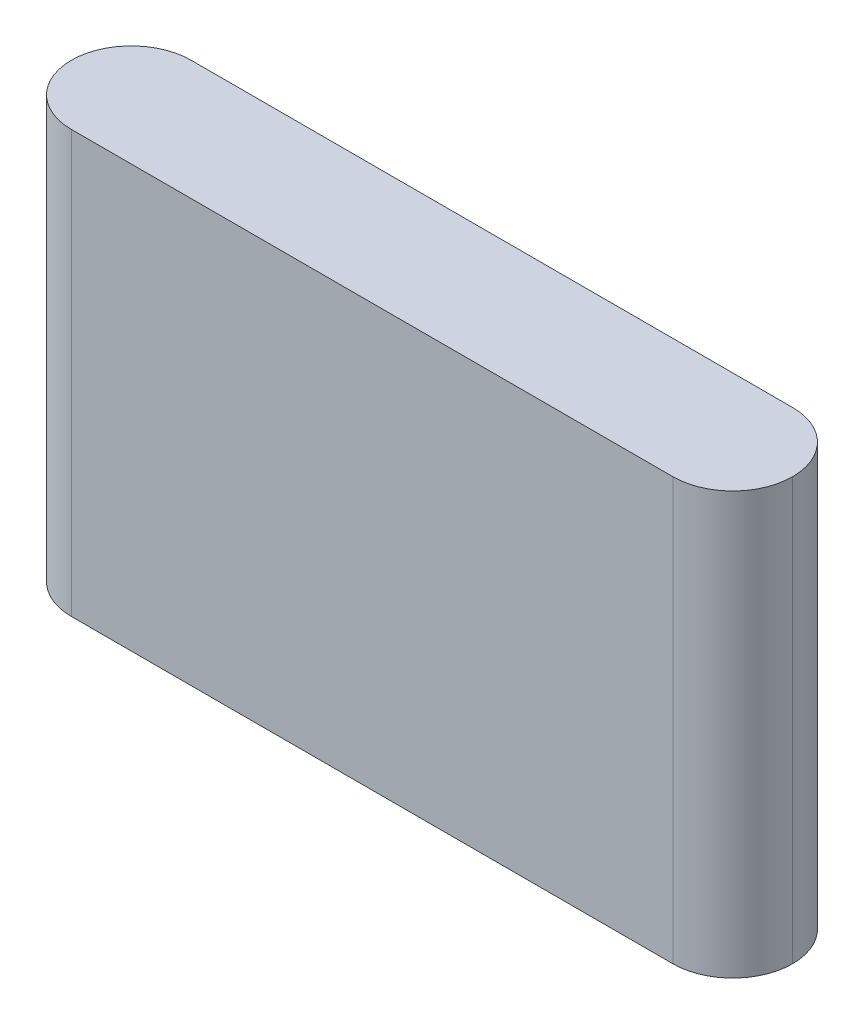
SolidWorks part; units mm, degrees
material "Custom Plastic"
ref_plane "Front Plane" through (0, 0, 0) normal (0, 0, 1) x (1, 0, 0)
ref_plane "Top Plane" through (0, 0, 0) normal (0, 1, 0) x (1, 0, 0)
ref_plane "Right Plane" through (0, 0, 0) normal (1, 0, 0) x (0, 0, -1)
sketch "Sketch1" plane through (0, 0, 0) normal (0, 1, 0) x (1, 0, 0)
  line L1 (-42.75, 7.1) -> (42.75, 7.1)
  line L2 (-42.75, 7.1) -> (-42.75, -7.1)
  line L3 (-42.75, -7.1) -> (42.75, -7.1)
  line L4 (42.75, 7.1) -> (42.75, -7.1)
  line L5 (-42.75, 7.1) -> (42.75, -7.1) construction
  line L6 (-42.75, -7.1) -> (42.75, 7.1) construction
  point P0 (0, 0)
  dimension "D1" = 14.2
  dimension "D2" = 85.5
extrude "Boss-Extrude1" add sketch "Sketch1" along normal blind 50
fillet "Fillet1" radius 7.1 4 edges at (42.75, 25, -7.1) (42.75, 25, 7.1) (-42.75, 25, -7.1) (-42.75, 25, 7.1)
